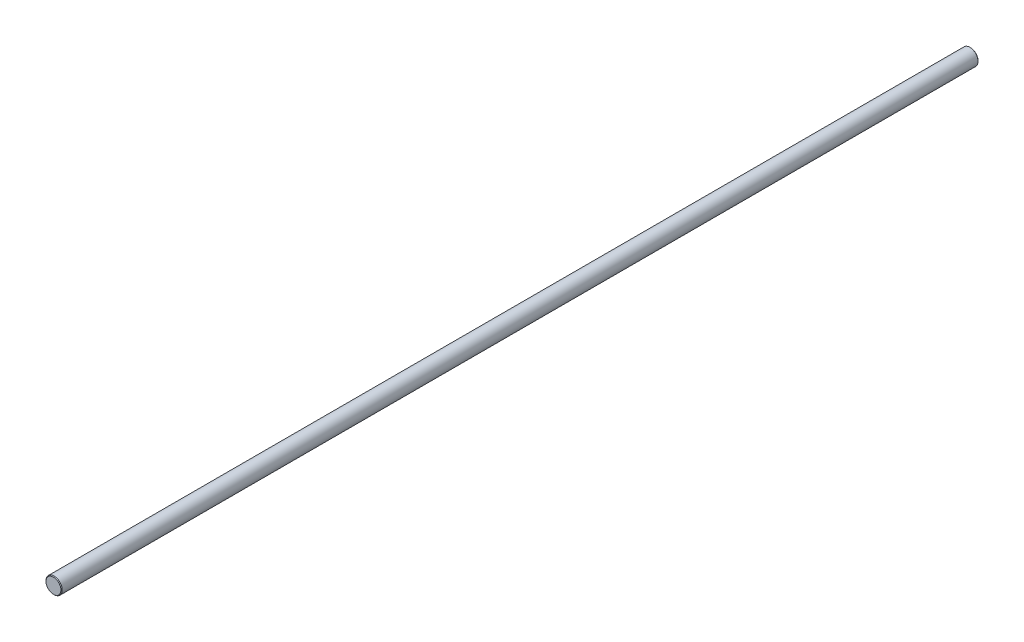
SolidWorks part; units mm, degrees
material "AISI 304"
ref_plane "Спереди" through (0, 0, 0) normal (0, 0, 1) x (1, 0, 0)
ref_plane "Сверху" through (0, 0, 0) normal (0, 1, 0) x (1, 0, 0)
ref_plane "Справа" through (0, 0, 0) normal (1, 0, 0) x (0, 0, -1)
ref_axis "ОсьX" through (-88.99, 0, 0) along (1, 0, 0)
ref_axis "ОсьZ" through (0, 55, 0) along (0, -1, 0)
ref_axis "ОсьY" through (0, 0, -88.99) along (0, 0, 1)
sketch "Эскиз1" plane through (0, 0, 0) normal (0, 0, 1) x (1, 0, 0)
  circle A0 centre (0, 0) radius 12.5
  dimension "D1" = 25
extrude "Бобышка-Вытянуть1" add sketch "Эскиз1" along normal mid plane 1414
chamfer "Фаска1" distance 1 angle 45 2 edges at (12.5, 0, -707) (12.5, 0, 707)
